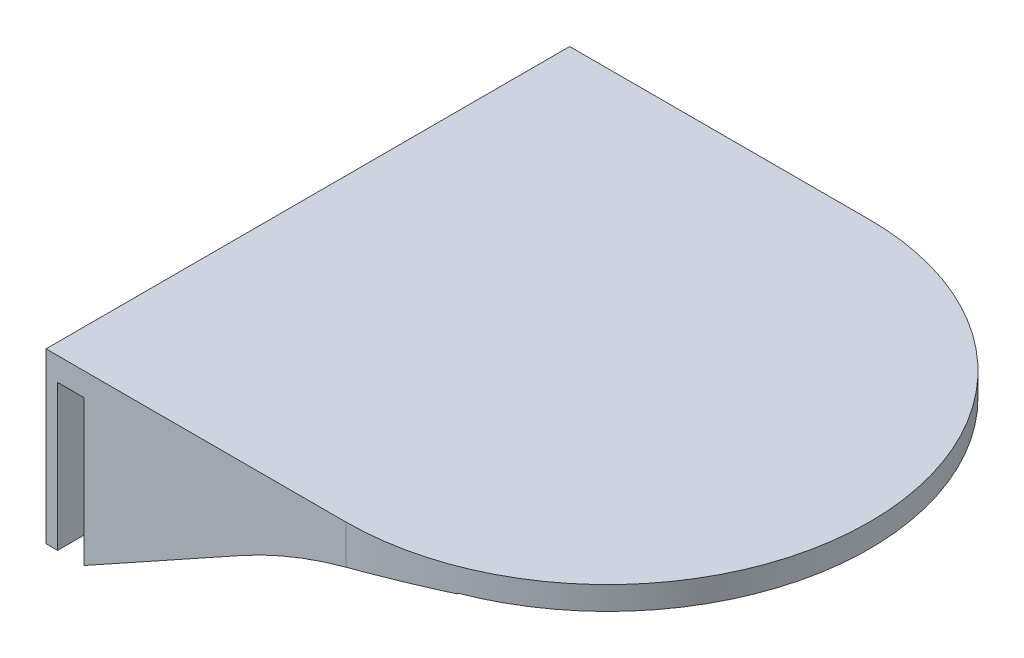
SolidWorks part; units mm, degrees
ref_plane "Front Plane" through (0, 0, 0) normal (0, 0, 1) x (1, 0, 0)
ref_plane "Top Plane" through (0, 0, 0) normal (0, 1, 0) x (1, 0, 0)
ref_plane "Right Plane" through (0, 0, 0) normal (1, 0, 0) x (0, 0, -1)
sketch "Sketch1" plane through (0, 0, 0) normal (0, 1, 0) x (1, 0, 0)
  line L0 (-103.082, 40) -> (-103.082, -40) construction
  line L1 (0, 90) -> (-103.082, 90)
  line L3 (0, -90) -> (-103.082, -90)
  line L4 (-103.082, 90) -> (-103.082, -90)
  line L5 (-51.541, -90) -> (-51.541, 90) construction
  line L6 (16.918, 0) -> (-103.082, 0) construction
  arc A0 (0, -90) -> (0, 90) centre (0, 0) ccw
  point P503 (-51.541, 0)
  dimension "D1" = 180
extrude "Boss-Extrude1" add sketch "Sketch1" along normal blind 8
sketch "Sketch2" plane through (0, 0, 90) normal (0, 0, 1) x (1, 0, 0)
  line L5 (-103.082, 8) -> (-103.082, -50)
  line L6 (-103.082, -50) -> (-99.082, -50)
  line L11 (-99.082, -50) -> (-99.082, 0)
  line L12 (-103.082, 0) -> (0, 0) construction
  line L18 (-99.082, 0) -> (-90.082, 0)
  line L24 (-90.082, 0) -> (-90.082, -50)
  line L25 (-90.082, -50) -> (0, 0)
  line L26 (0, 0) -> (0, 8)
  line L27 (0, 8) -> (-103.082, 8)
  dimension "D1" = 9
  dimension "D2" = 4
  dimension "D3" = 50
extrude "Boss-Extrude2" add sketch "Sketch2" against normal up to surface (180 mm away) up to face at (-51.541, 4, -90)
sketch "Sketch8" plane through (0, 0, 0) normal (1, 0, 0) x (0, 0, -1)
  line L0 (90, 0) -> (-90, 0) construction
  line L1 (-84, 0) -> (84, 0)
  line L2 (-84, 0) -> (-84, -50)
  line L3 (-84, -50) -> (84, -50)
  line L4 (84, 0) -> (84, -50)
  line L5 (0, -50) -> (0, 0) construction
  line L6 (-84, -25) -> (84, -25) construction
  line L7 (90, -50) -> (-90, -50) construction
  point P412 (0, -25)
  dimension "D1" = 6
  dimension "D2" = 6
extrude "Cut-Extrude2" cut sketch "Sketch8" against normal up to surface (90.082 mm away) up to face at (-90.082, -25, 0)
fillet "Fillet4" radius 160 2 edges at (0, 0, -87) (0, 0, 87)
